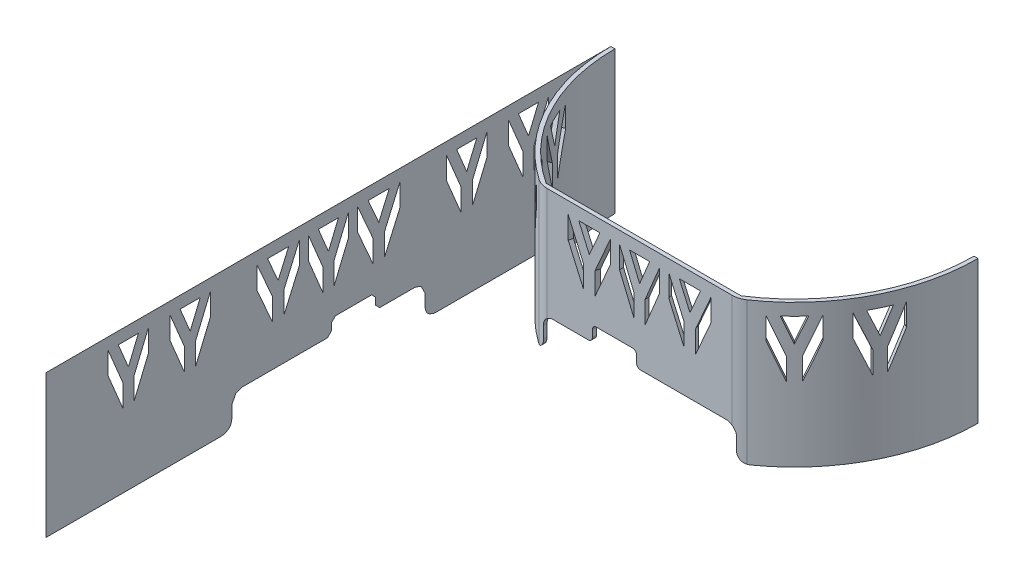
SolidWorks part; units mm, degrees
ref_plane "Front Plane" through (0, 0, 0) normal (0, 0, 1) x (1, 0, 0)
ref_plane "Top Plane" through (0, 0, 0) normal (0, 1, 0) x (1, 0, 0)
ref_plane "Right Plane" through (0, 0, 0) normal (1, 0, 0) x (0, 0, -1)
sketch "Sketch1" plane through (0, 0, 0) normal (0, 1, 0) x (1, 0, 0)
  line L0 (0, 124.168) -> (0, -125.7458) construction
  line L1 (-136.0011, 0) -> (148.623, 0) construction
  line L2 (-48.4715, -75) -> (48.4715, -75)
  line L3 (-49.058, -77) -> (49.058, -77)
  arc A0 (48.4715, -75) -> (-48.4715, -75) centre (0, 0) ccw
  arc A1 (49.058, -77) -> (-49.058, -77) centre (0, 0) ccw
  dimension "D1" = 178.6
  dimension "D3" = 182.6
  dimension "D2" = 75
  dimension "D4" = 77
extrude "Boss-Extrude1" add sketch "Sketch1" along normal blind 71
fillet "Fillet1" radius 10 2 edges at (-49.058, 35.5, 77) (49.058, 35.5, 77)
sketch "Sketch2" plane through (0, 0, 77) normal (0, 0, 1) x (1, 0, 0)
  line L0 (0, 94.4811) -> (0, -36.6428) construction
  line L1 (46.051, 0) -> (51.7153, 0) construction
  line L2 (-48, 16) -> (48, 16)
  line L4 (-48, 16) -> (-48, 0)
  line L5 (-48, 0) -> (48, 0)
  line L6 (48, 16) -> (48, 0)
  line L7 (-48, 16) -> (48, 0) construction
  line L8 (-48, 0) -> (48, 16) construction
  line L9 (-46.051, 71) -> (46.051, 71) construction
  point P3 (0, 8)
  dimension "D1" = 55
  dimension "D2" = 96
extrude "Cut-Extrude1" cut sketch "Sketch2" against normal blind 5
sketch "Sketch3" plane through (0, 0, 77) normal (0, 0, 1) x (1, 0, 0)
  line L0 (0, 94.4811) -> (0, -26.607) construction
  line L1 (46.051, 16) -> (-46.051, 16) construction
  line L2 (-23.5, 16) -> (-1.5, 16)
  line L3 (-23.5, 16) -> (-23.5, 23.5)
  line L4 (-23.5, 23.5) -> (-1.5, 23.5)
  line L5 (-1.5, 16) -> (-1.5, 23.5)
  dimension "D1" = 22
  dimension "D2" = 7.5
  dimension "D3" = 1.5
extrude "Cut-Extrude2" cut sketch "Sketch3" against normal blind 5
fillet "Fillet2" radius 5 4 edges at (-48, 16, 75.9041) (-48, 0, 75.9041) (48, 16, 75.9041) (48, 0, 75.9041)
fillet "Fillet3" radius 2 4 edges at (-1.5, 16, 76) (-1.5, 23.5, 76) (-23.5, 16, 76) (-23.5, 23.5, 76)
sketch "Sketch4" plane through (0, 0, 0) normal (0, 0, 1) x (1, 0, 0)
  line L0 (0, 103.2008) -> (0, -37.4655) construction
  line L1 (-5, 65) -> (5, 65)
  line L2 (-5, 65) -> (0, 53)
  line L3 (0, 53) -> (5, 65)
  line L8 (-46.051, 71) -> (46.051, 71) construction
  line L9 (-10, 65) -> (-2.75, 47.6)
  line L10 (-2.75, 47.6) -> (-2.75, 36.6)
  line L11 (-2.75, 36.6) -> (-10, 54)
  line L12 (-10, 54) -> (-10, 65)
  line L13 (10, 65) -> (2.75, 47.6)
  line L14 (2.75, 47.6) -> (2.75, 36.6)
  line L15 (2.75, 36.6) -> (10, 54)
  line L16 (10, 54) -> (10, 65)
  point P6 (0, 65)
  dimension "D1" = 10
  dimension "D2" = 6
  dimension "D3" = 5
  dimension "D4" = 11
  dimension "D5" = 12
  dimension "D6" = 2.75
extrude "Cut-Extrude3" cut sketch "Sketch4" against normal blind 132
pattern_circular "CirPattern1" count 20 over 360 about axis through (0, 71, 0) along (0, 1, 0) skipping 1, 2, 3, 4, 5, 6, 7, 8, 12, 13, 14, 15, 16, 17, 18, 19 of "Cut-Extrude3"
pattern_circular "CirPattern2" count 16 over 360 about axis through (0, 71, 0) along (0, 1, 0) skipping 1, 2, 3, 4, 5, 7, 8, 9, 11, 12, 13, 14, 15 of "Cut-Extrude3"
pattern_circular "CirPattern3" count 28 over 360 about axis through (0, 71, 0) along (0, 1, 0) skipping 1, 2, 3, 4, 5, 6, 7, 8, 10, 11, 12, 13, 14, 15, 16, 17, 18, 20, 21, 22, 23, 24, 25, 26, 27 of "Cut-Extrude3"
sketch "Sketch6" plane through (0, 0, 0) normal (0, 1, 0) x (1, 0, 0)
  line L0 (-100.8658, 0) -> (109.8927, 0) construction
  line L1 (-46.051, -77) -> (46.051, -77) construction
  line L3 (-100.8658, 0) -> (109.8927, 0)
  line L4 (-100.8658, 0) -> (-100.8658, 95.751)
  line L5 (-100.8658, 95.751) -> (109.8927, 95.751)
  line L6 (109.8927, 0) -> (109.8927, 95.751)
  dimension "D1" = 77
extrude "Cut-Extrude4" cut sketch "Sketch6" along normal blind 92
ref_plane "Plane1" through (89.3, 0, 0) normal (-1, 0, 0) x (0, 0, 1)
ref_plane "Plane2" through (-89.3, 0, 0) normal (1, 0, 0) x (0, 0, -1)
surface "Surface-Flatten2"
sketch "Sketch7" plane through (-91.3, 0, 0) normal (-1, 0, 0) x (0, 0, 1)
  line L14 (81.7673, 65.001) -> (81.7672, 54.0009)
  line L15 (71.7481, 53.0006) -> (66.7459, 65.0008)
  line L16 (81.7672, 54.0009) -> (74.4984, 36.6008)
  line L17 (68.9977, 36.6004) -> (61.7286, 54.0004)
  line L18 (61.7285, 65.0005) -> (68.9978, 47.6004)
  line L19 (61.7286, 54.0004) -> (61.7285, 65.0005)
  line L20 (74.4984, 47.6004) -> (81.7673, 65.001)
  line L21 (68.9978, 47.6004) -> (68.9977, 36.6004)
  line L22 (66.7459, 65.0008) -> (76.7502, 65.001)
  line L23 (76.7502, 65.001) -> (71.7481, 53.0006)
  line L24 (74.4984, 36.6008) -> (74.4984, 47.6004)
  line L25 (150.4825, 53.997) -> (143.2136, 36.5969)
  line L26 (137.7129, 36.5965) -> (130.4439, 53.9965)
  line L27 (130.4439, 53.9965) -> (130.4437, 64.9966)
  line L28 (137.7131, 47.5965) -> (137.7129, 36.5965)
  line L29 (150.4825, 64.9971) -> (150.4825, 53.997)
  line L30 (135.4612, 64.9969) -> (145.4655, 64.9971)
  line L31 (130.4437, 64.9966) -> (137.7131, 47.5965)
  line L32 (145.4655, 64.9971) -> (140.4634, 52.9967)
  line L33 (140.4634, 52.9967) -> (135.4612, 64.9969)
  line L34 (143.2136, 36.5969) -> (143.2136, 47.5965)
  line L35 (143.2136, 47.5965) -> (150.4825, 64.9971)
  line L36 (204.2599, 64.9898) -> (214.2642, 64.99)
  line L37 (199.2424, 64.9895) -> (206.5118, 47.5894)
  line L38 (212.0124, 47.5894) -> (219.2812, 64.99)
  line L39 (212.0124, 36.5898) -> (212.0124, 47.5894)
  line L40 (219.2812, 64.99) -> (219.2812, 53.9899)
  line L41 (214.2642, 64.99) -> (209.2621, 52.9896)
  line L42 (209.2621, 52.9896) -> (204.2599, 64.9898)
  line L43 (219.2812, 53.9899) -> (212.0124, 36.5898)
  line L44 (206.5118, 47.5894) -> (206.5116, 36.5894)
  line L45 (206.5116, 36.5894) -> (199.2426, 53.9894)
  line L46 (199.2426, 53.9894) -> (199.2424, 64.9895)
  line L47 (234.99, 64.9846) -> (244.9943, 64.9848)
  line L48 (237.2419, 47.5842) -> (237.2418, 36.5842)
  line L49 (242.7425, 36.5846) -> (242.7425, 47.5842)
  line L50 (237.2418, 36.5842) -> (229.9727, 53.9842)
  line L51 (250.0113, 53.9847) -> (242.7425, 36.5846)
  line L52 (229.9726, 64.9843) -> (237.2419, 47.5842)
  line L53 (242.7425, 47.5842) -> (250.0114, 64.9848)
  line L54 (239.9922, 52.9843) -> (234.99, 64.9846)
  line L55 (244.9943, 64.9848) -> (239.9922, 52.9843)
  line L56 (250.0114, 64.9848) -> (250.0113, 53.9847)
  line L57 (229.9727, 53.9842) -> (229.9726, 64.9843)
  line L64 (51.0776, 65.001) -> (51.0775, 54.0009)
  line L69 (41.0585, 53.0006) -> (36.0563, 65.0008)
  line L70 (38.308, 36.6004) -> (31.039, 54.0004)
  line L71 (31.0388, 65.0005) -> (38.3081, 47.6004)
  line L72 (38.3081, 47.6004) -> (38.308, 36.6004)
  line L73 (43.8087, 36.6008) -> (43.8087, 47.6004)
  line L74 (46.0605, 65.001) -> (41.0585, 53.0006)
  line L75 (51.0775, 54.0009) -> (43.8087, 36.6008)
  line L76 (36.0563, 65.0008) -> (46.0605, 65.001)
  line L77 (31.039, 54.0004) -> (31.0388, 65.0005)
  line L78 (43.8087, 47.6004) -> (51.0776, 65.001)
  line L80 (0, 0) -> (92.4643, 0)
  line L82 (0, 0) -> (0, 70.9795)
  line L83 (0, 70.9795) -> (280.9661, 70.9795)
  line L86 (280.9661, 0) -> (280.9661, 70.9795)
  line L90 (92.4643, 0) -> (92.4643, 16)
  line L94 (92.4643, 16) -> (116.9794, 16)
  line L99 (154.987, 64.9906) -> (162.6093, 47.5904)
  line L100 (176.016, 53.9894) -> (168.3918, 36.5899)
  line L101 (154.987, 64.9906) -> (154.9863, 53.991)
  line L102 (162.6093, 47.5904) -> (162.6088, 36.5904)
  line L103 (170.7591, 64.9899) -> (160.2443, 64.9906)
  line L104 (168.3924, 47.59) -> (176.0165, 64.9895)
  line L105 (154.9863, 53.991) -> (162.6088, 36.5904)
  line L106 (168.3918, 36.5899) -> (168.3924, 47.59)
  line L107 (170.7591, 64.9899) -> (165.5011, 52.9902)
  line L108 (176.0165, 64.9895) -> (176.016, 53.9894)
  line L109 (160.2443, 64.9906) -> (165.5011, 52.9902)
  line L110 (188.4914, 0) -> (188.4914, 16)
  line L113 (116.9794, 16) -> (116.9794, 23.5)
  line L114 (116.9794, 23.5) -> (138.9792, 23.5)
  line L115 (138.9792, 16) -> (138.9792, 23.5)
  line L116 (104.95, 64.9962) -> (112.5724, 47.596)
  line L117 (125.9796, 64.9951) -> (125.979, 53.9951)
  line L119 (104.95, 64.9962) -> (104.9494, 53.9967)
  line L120 (120.7222, 64.9955) -> (115.4642, 52.9959)
  line L121 (125.979, 53.9951) -> (118.3549, 36.5956)
  line L122 (118.3554, 47.5957) -> (125.9796, 64.9951)
  line L123 (118.3549, 36.5956) -> (118.3554, 47.5957)
  line L124 (104.9494, 53.9967) -> (112.5719, 36.596)
  line L125 (110.2073, 64.9962) -> (115.4642, 52.9959)
  line L126 (120.7222, 64.9955) -> (110.2073, 64.9962)
  line L127 (112.5724, 47.596) -> (112.5719, 36.596)
  line L128 (188.4914, 0) -> (280.9661, 0)
  line L129 (138.9792, 16) -> (188.4914, 16)
